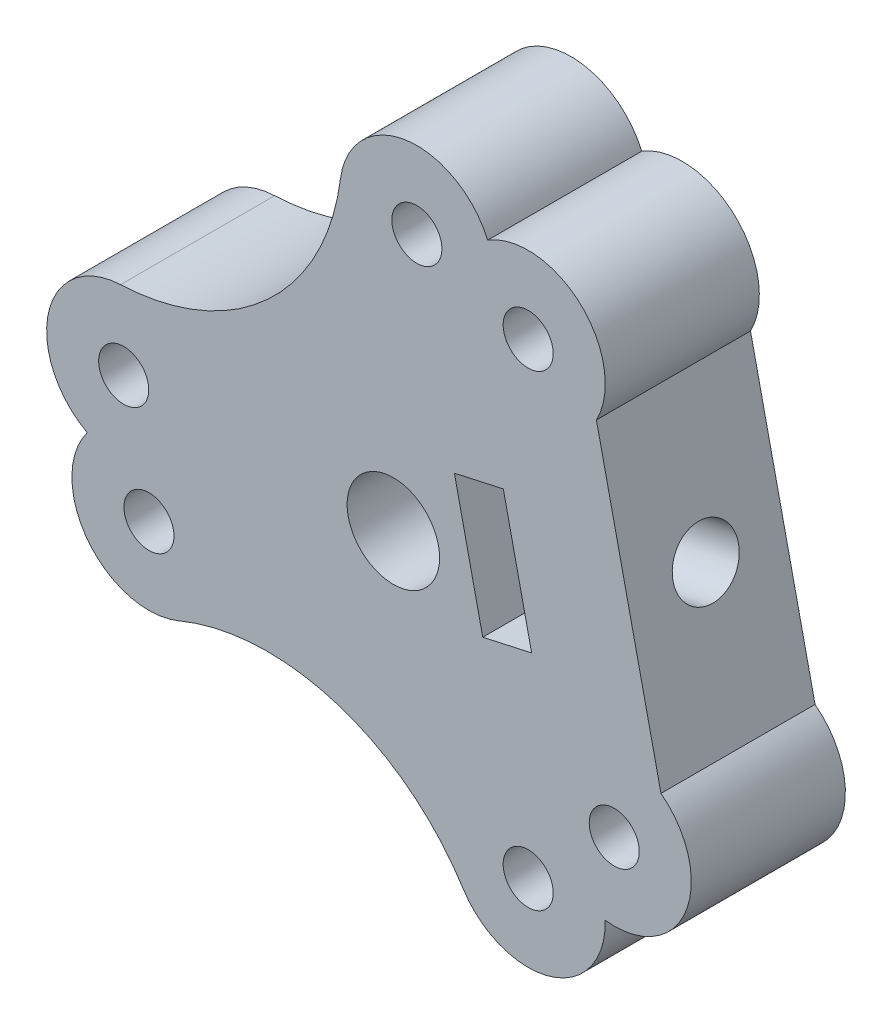
SolidWorks part; units mm, degrees
ref_plane "Front Plane" through (0, 0, 0) normal (0, 0, 1) x (1, 0, 0)
ref_plane "Top Plane" through (0, 0, 0) normal (0, 1, 0) x (1, 0, 0)
ref_plane "Right Plane" through (0, 0, 0) normal (1, 0, 0) x (0, 0, -1)
sketch "Sketch1" plane through (0, 0, 0) normal (0, 0, 1) x (1, 0, 0)
  line L0 (-17.78, 5.08) -> (0, 5.08)
  line L2 (0, -5.08) -> (-17.78, -5.08)
  circle A0 centre (0, 0) radius 3.048
  circle A1 centre (-17.78, 0) radius 1.651
  arc A2 (-17.78, 5.08) -> (-17.78, -5.08) centre (-17.78, 0) ccw
  arc A3 (0, -5.08) -> (0, 5.08) centre (0, 0) ccw
  dimension "D1" = 6.096
  dimension "D2" = 10.16
  dimension "D3" = 3.302
  dimension "D4" = 17.78
extrude "Boss-Extrude1" add sketch "Sketch1" along normal blind 10.16
pattern_circular "CirPattern1" count 2 every 25 about axis through (0, 0, 10.16) along (0, 0, 1) of "Boss-Extrude1"
pattern_circular "CirPattern2" count 3 over 360 about axis through (0, 0, 0) along (0, 0, 1) of "Boss-Extrude1", "CirPattern1"
fillet "Fillet1" radius 15.24 21 edges at (-11.2175, 5.08, 0) (-11.2175, 5.08, 10.16) (-4.083, 11.6175, 0) (-4.655, 5.08, 5.08) (-3.511, 18.1551, 5.08) (-4.083, 11.6175, 10.16) (-8.0196, -9.3448, 10.16) (-8.0196, -9.3448, 0) (-13.9673, -12.1182, 5.08) (-2.0719, -6.5713, 5.08) (1.2093, -12.2546, 10.16) (1.2093, -12.2546, 0) (4.4906, -17.9379, 5.08) (13.2894, 12.8579, 5.08) (-17.78, 5.08, 5.08) (10.0081, 7.1746, 10.16) (10.0081, 7.1746, 0) (6.7269, 1.4913, 5.08) (12.1026, -2.2728, 10.16) (12.1026, -2.2728, 0) (17.4783, -6.0369, 5.08)
sketch "Sketch4" plane through (0, 0, 10.16) normal (0, 0, 1) x (1, 0, 0)
  line L0 (4.025, 5.3152) -> (5.8942, -3.1161)
  line L1 (5.8942, -3.1161) -> (9.1179, -2.4014)
  line L2 (9.1179, -2.4014) -> (7.2487, 6.0298)
  line L3 (7.2487, 6.0298) -> (4.025, 5.3152)
  line L4 (4.9596, 1.0995) -> (8.1833, 1.8142) construction
  line L5 (0, 0) -> (12.0066, 2.6618) construction
  arc A0 (13.3889, 13.0385) -> (17.6447, -6.1586) centre (26.8854, 5.9603) ccw construction
  dimension "D1" = 8.636
  dimension "D2" = 3.302
  dimension "D3" = 5.08
extrude "Cut-Extrude1" cut sketch "Sketch4" against normal blind 9.398
ref_plane "Plane2" through (16.6868, 3.6994, 0) normal (0.9763, 0.2164, 0) x (0, 0, -1)
sketch "Sketch7" plane through (16.6868, 3.6994, 0) normal (0.9763, 0.2164, 0) x (0, 0, -1)
  line L1 (0, 9.8316) -> (-10.16, 9.8316)
  line L2 (0, 9.8316) -> (0, -9.8316)
  line L3 (0, -9.8316) -> (-10.16, -9.8316)
  line L4 (-10.16, 9.8316) -> (-10.16, -9.8316)
extrude "Boss-Extrude3" add sketch "Sketch7" against normal up to surface (1.1985 mm away)
sketch "Sketch8" plane through (16.6868, 3.6994, 0) normal (0.9763, 0.2164, 0) x (0, 0, -1)
  line L1 (0, 9.8316) -> (-10.16, 9.8316)
  line L2 (0, 9.8316) -> (0, -9.8316)
  line L3 (0, -9.8316) -> (-10.16, -9.8316)
  line L4 (-10.16, 9.8316) -> (-10.16, -9.8316)
extrude "Cut-Extrude3" cut sketch "Sketch8" against normal up to vertex (43.8435 mm away)
sketch "Sketch5" plane through (16.6868, 3.6994, 0) normal (0.9763, 0.2164, 0) x (0, 0, -1)
  line L0 (-5.08, 0) -> (-10.16, 0) construction
  circle A0 centre (-5.08, 0) radius 2.159
  dimension "D2" = 4.318
  dimension "D1" = 5.08
extrude "Cut-Extrude2" cut sketch "Sketch5" against normal up to surface (14.9405 mm away)
